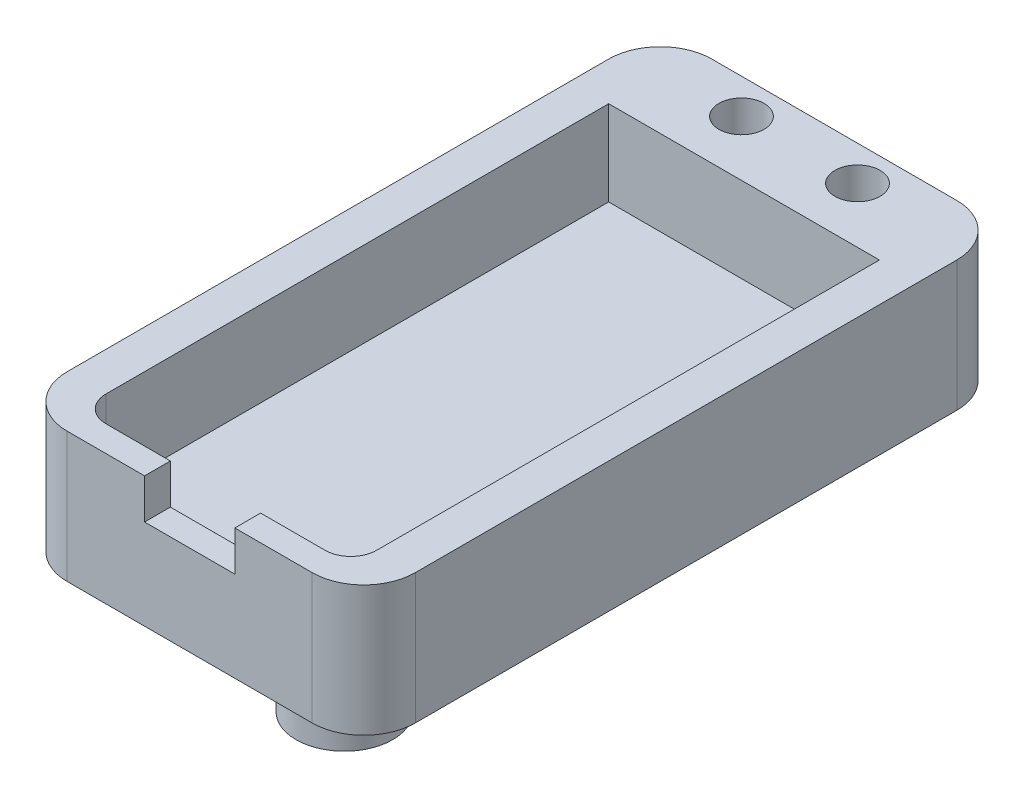
SolidWorks part; units mm, degrees
ref_plane "Front Plane" through (0, 0, 0) normal (0, 0, 1) x (1, 0, 0)
ref_plane "Top Plane" through (0, 0, 0) normal (0, 1, 0) x (1, 0, 0)
ref_plane "Right Plane" through (0, 0, 0) normal (1, 0, 0) x (0, 0, -1)
sketch "Sketch1" plane through (0, 0, 0) normal (0, 1, 0) x (1, 0, 0)
  line L1 (0, 41) -> (27, 41)
  line L2 (0, 41) -> (0, 0)
  line L3 (0, 0) -> (27, 0)
  line L4 (27, 41) -> (27, 0)
  dimension "D1" = 27
  dimension "D2" = 41
extrude "Boss-Extrude1" add sketch "Sketch1" along normal blind 3.5
sketch "Sketch2" plane through (0, 3.5, 0) normal (0, 1, 0) x (1, 0, 0)
  line L0 (27, 41) -> (0, 41) construction
  line L1 (0, 0) -> (3, 0)
  line L2 (0, 0) -> (0, 41)
  line L3 (0, 41) -> (3, 41)
  line L4 (3, 0) -> (3, 41)
  line L5 (0, 0) -> (27, 0) construction
  line L6 (27, 41) -> (24, 41)
  line L7 (27, 41) -> (27, 0)
  line L8 (27, 0) -> (24, 0)
  line L9 (24, 41) -> (24, 0)
  dimension "D2" = 3
extrude "Boss-Extrude2" add sketch "Sketch2" along normal blind 7.5
sketch "Sketch3" plane through (0, 0, 0) normal (0, -1, 0) x (-1, 0, 0)
  line L0 (0, 0) -> (-27, 0) construction
  circle A0 centre (-13.5, 10) radius 3.75
  point P2 (-13.5, 0)
  dimension "D1" = 7.5
  dimension "D2" = 10
extrude "Boss-Extrude3" add sketch "Sketch3" along normal blind 10
sketch "Sketch4" plane through (0, 0, -41) normal (0, 0, -1) x (-1, 0, 0)
  line L1 (-27, 11) -> (0, 11)
  line L2 (-27, 11) -> (-27, 0)
  line L3 (-27, 0) -> (0, 0)
  line L4 (0, 11) -> (0, 0)
extrude "Boss-Extrude4" add sketch "Sketch4" along normal blind 2 contours L1 L4 L3 L2
sketch "Sketch5" plane through (0, 0, 0) normal (0, 0, 1) x (1, 0, 0)
  line L1 (0, 11) -> (27, 11)
  line L2 (0, 11) -> (0, 0)
  line L3 (0, 0) -> (27, 0)
  line L4 (27, 11) -> (27, 0)
extrude "Boss-Extrude5" add sketch "Sketch5" along normal blind 2
sketch "Sketch6" plane through (0, 0, 2) normal (0, 0, 1) x (1, 0, 0)
  line L0 (27, 11) -> (0, 11) construction
  line L1 (10, 11) -> (17, 11)
  line L2 (10, 11) -> (10, 7)
  line L3 (10, 7) -> (17, 7)
  line L4 (17, 11) -> (17, 7)
  line L5 (9.75, 0) -> (17.25, 0) construction
  point P6 (13.5, 0)
  point P7 (13.5, 7)
  dimension "D1" = 4
  dimension "D2" = 7
extrude "Cut-Extrude1" cut sketch "Sketch6" against normal up to next
sketch "Sketch7" plane through (0, 0, -43) normal (0, 0, -1) x (-1, 0, 0)
  line L1 (-27, 11) -> (0, 11)
  line L2 (-27, 11) -> (-27, 0)
  line L3 (-27, 0) -> (0, 0)
  line L4 (0, 11) -> (0, 0)
extrude "Boss-Extrude6" add sketch "Sketch7" along normal blind 5
sketch "Sketch8" plane through (0, 11, 0) normal (0, 1, 0) x (1, 0, 0)
  line L0 (0, 48) -> (27, 48) construction
  circle A0 centre (18, 45.3) radius 1.75
  circle A1 centre (9, 45.3) radius 1.75
  point P7 (13.5, 48)
  dimension "D1" = 3.5
  dimension "D2" = 2.7
  dimension "D3" = 9
  dimension "D4" = 4.5
extrude "Cut-Extrude2" cut sketch "Sketch8" against normal through all
sketch "Sketch9" plane through (0, 11, 0) normal (0, 1, 0) x (1, 0, 0)
  line L1 (0, 48) -> (27, 48)
  line L2 (0, 48) -> (0, -2)
  line L3 (0, -2) -> (27, -2)
  line L4 (27, 48) -> (27, -2)
extrude "Cut-Extrude3" cut sketch "Sketch9" against normal blind 0.9
fillet "Fillet1" radius 4 4 edges at (0, 5.05, -48) (27, 5.05, -48) (27, 5.05, 2) (0, 5.05, 2)
fillet "Fillet2" radius 2 2 edges at (24, 6.8, 0) (3, 6.8, 0)
